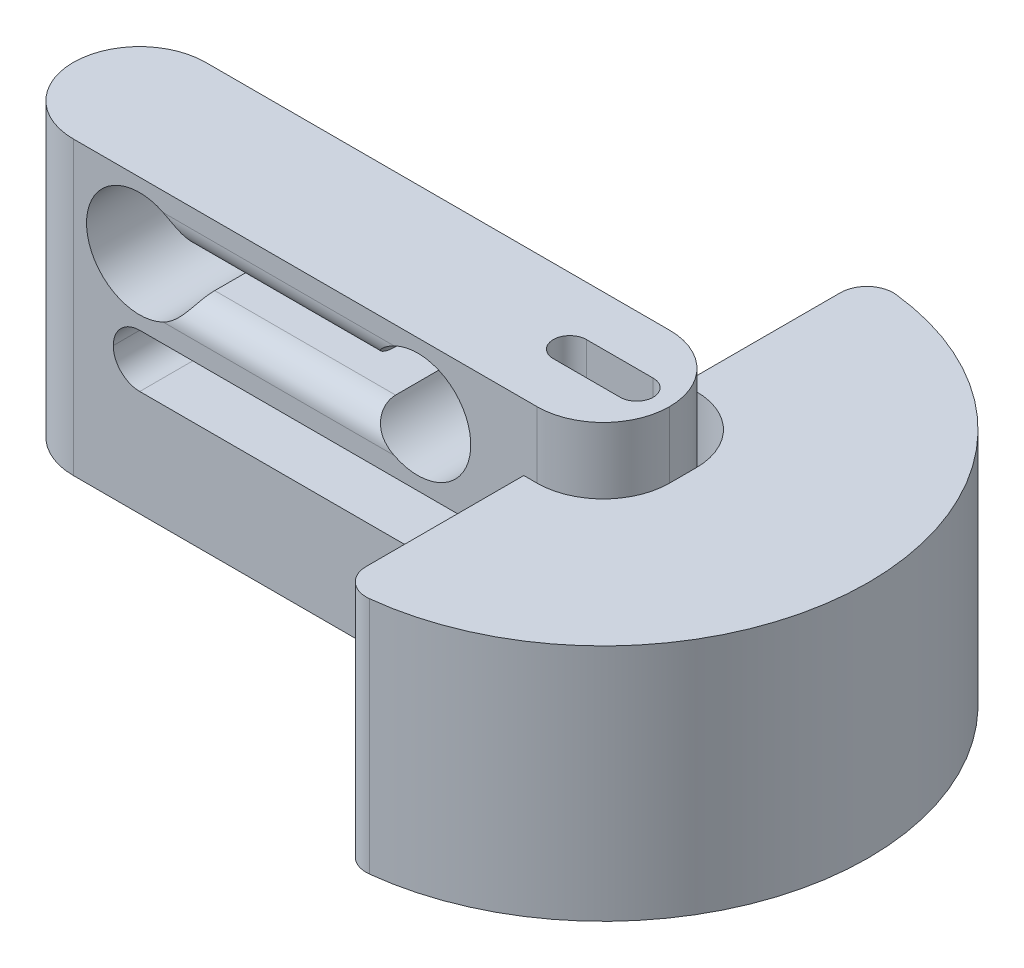
SolidWorks part; units mm, degrees
ref_plane "Front Plane" through (0, 0, 0) normal (0, 0, 1) x (1, 0, 0)
ref_plane "Top Plane" through (0, 0, 0) normal (0, 1, 0) x (1, 0, 0)
ref_plane "Right Plane" through (0, 0, 0) normal (1, 0, 0) x (0, 0, -1)
other "Center of Mass"
sketch "Sketch1" plane through (0, 0, 0) normal (0, 0, 1) x (1, 0, 0)
  line L0 (5, 0) -> (0, 0)
  line L1 (0, 0) -> (-5, 0)
  line L2 (-5, 0) -> (-35, 0)
  line L3 (5, 0) -> (5, -10)
  line L4 (5, -10) -> (-5, -10)
  line L5 (-5, -10) -> (-31.9826, -10)
  line L6 (-35, 0) -> (-40, 0)
  line L7 (-26.8791, -3.4207) -> (-11.5008, -3.4207)
  line L8 (-26.8791, -3.4207) -> (-26.8791, -6.5793)
  line L9 (-26.8791, -6.5793) -> (-11.5008, -6.5793)
  line L10 (-11.5008, -3.4207) -> (-11.5008, -6.5793)
  line L11 (-26.8791, -3.4207) -> (-11.5008, -6.5793) construction
  line L12 (-26.8791, -6.5793) -> (-11.5008, -3.4207) construction
  line L13 (-40, 0) -> (-40, -14)
  line L14 (-40, -14) -> (-31.9826, -14)
  line L15 (-31.9826, -14) -> (-31.9826, -10)
  circle A0 centre (-30, -5) radius 4
  circle A1 centre (-9, -5) radius 4
  point P12 (-19.1899, -5)
  dimension "D5" = 5
  dimension "D6" = 5
  dimension "D7" = 8
  dimension "D8" = 8
  dimension "D1" = 5
  dimension "D2" = 5
  dimension "D3" = 30
  dimension "D4" = 10
  dimension "D9" = 4
  dimension "D10" = 40
  dimension "D11" = 14
extrude "Boss-Extrude1" add sketch "Sketch1" along normal blind 5 and the other way blind 5 contours L14 L15 L5 L4 L3 L0 L1 L2 L6 L13 A1 L9 A0 L7 region at (4.5287, -5, 0)
sketch "Sketch2" plane through (0, 0, 0) normal (0, 1, 0) x (1, 0, 0)
  line L0 (-2.521, 0) -> (2.521, 0) construction
  line L1 (-2.521, 1.25) -> (2.521, 1.25)
  line L2 (-2.521, -1.25) -> (2.521, -1.25)
  arc A0 (-2.521, 1.25) -> (-2.521, -1.25) centre (-2.521, 0) ccw
  arc A1 (2.521, -1.25) -> (2.521, 1.25) centre (2.521, 0) ccw
  point P2 (0, 0)
extrude "Cut-Extrude1" cut sketch "Sketch2" against normal blind 5
sketch "Sketch3" plane through (0, 0, 0) normal (0, 1, 0) x (1, 0, 0)
  line L0 (5, -5) -> (-40, -5) construction
  line L1 (-40, 5) -> (5.8816, 5)
  line L2 (-40, 5) -> (-40, -5)
  line L3 (-40, -5) -> (5.8816, -5)
  line L4 (5.8816, 5) -> (5.8816, -5)
  line L6 (-44.7352, 22.5342) -> (0, 22.5342)
  line L7 (-44.7352, 22.5342) -> (-44.7352, -27.8282)
  line L8 (-44.7352, -27.8282) -> (0, -27.8282)
  line L9 (0, 22.5342) -> (0, -27.8282)
  circle A0 centre (0, 0) radius 20
  dimension "D1" = 40
extrude "Boss-Extrude2" add sketch "Sketch3" against normal blind 8 from offset 14 contours L9 A0 L1 L4 L3 | L1 L9 L3 L4 | L1 A0 L3 L9 | A0 L1 L2 L3 region at (-29.894, 0, 0) region at (-9.8957, 0, 0) region at (9.0612, 0, 0) region at (2.9408, 0, 0) offset against normal yes
sketch "Sketch4" plane through (0, -14, 0) normal (0, 1, 0) x (1, 0, 0)
  line L0 (5, 5) -> (-40, 5) construction
  line L1 (0, 20) -> (46.8504, 20)
  line L2 (0, 20) -> (0, -35.9681)
  line L3 (0, -35.9681) -> (46.8504, -35.9681)
  line L4 (46.8504, 20) -> (46.8504, -35.9681)
  line L5 (6, 6) -> (-6.1468, 6)
  line L6 (6, 6) -> (6, -6)
  line L7 (6, -6) -> (-6.1468, -6)
  line L8 (-6.1468, 6) -> (-6.1468, -6)
  line L9 (5, -5) -> (-40, -5) construction
  line L10 (5, 5) -> (5, -5) construction
  circle A0 centre (0, 0) radius 20
  arc M8 (0, -20) -> (0, 20) centre (0, 0) ccw
  line M9 (0, 20) -> (0, 5)
  dimension "D4" = 40
  dimension "D1" = 1
  dimension "D2" = 1
  dimension "D3" = 1
extrude "Boss-Extrude3" add sketch "Sketch4" along normal blind 10 contours L6 L7 L2 L5 M8 M9 region at (9.1986, -14, 0)
fillet "Fillet2" radius 5 6 edges at (-40, -11, -5) (-40, -11, 5) (6, -9, 6) (6, -9, -6) (5, -5, 5) (5, -5, -5)
fillet "Fillet3" radius 2 8 edges at (-19.5, -3.4207, -5) (-19.5, -6.5793, -5) (-19.5, -6.5793, 5) (-19.5, -3.4207, 5) (-31.9826, -10, 0) (-31.9826, -14, 0) (0, -13, -20) (0, -13, 20)
sketch "Sketch5" plane through (0, -22, 0) normal (0, -1, 0) x (1, 0, 0)
  line L0 (-35, 0) -> (-12, 0) construction
  line L1 (-35, 3.25) -> (-12, 3.25)
  line L2 (-35, -3.25) -> (-12, -3.25)
  line L4 (-6.5, 1.5) -> (-3.5, 1.5)
  line L5 (-6.5, 1.5) -> (-6.5, -1.5)
  line L6 (-6.5, -1.5) -> (-3.5, -1.5)
  line L7 (-3.5, 1.5) -> (-3.5, -1.5)
  line L8 (-6.5, 1.5) -> (-3.5, -1.5) construction
  line L9 (-6.5, -1.5) -> (-3.5, 1.5) construction
  line L10 (3.5, 1.5) -> (6.5, 1.5)
  line L11 (3.5, 1.5) -> (3.5, -1.5)
  line L12 (3.5, -1.5) -> (6.5, -1.5)
  line L13 (6.5, 1.5) -> (6.5, -1.5)
  line L14 (3.5, 1.5) -> (6.5, -1.5) construction
  line L15 (3.5, -1.5) -> (6.5, 1.5) construction
  arc A0 (-35, 3.25) -> (-35, -3.25) centre (-35, 0) ccw
  arc A1 (-12, -3.25) -> (-12, 3.25) centre (-12, 0) ccw
  circle A3 centre (0, 0) radius 2
  point P3 (-23.5, 0)
  point P8 (-5, 0)
  point P13 (5, 0)
  dimension "D3" = 3
  dimension "D9" = 4
  dimension "D1" = 35
  dimension "D2" = 12
  dimension "D4" = 3
  dimension "D5" = 0
  dimension "D6" = 5
  dimension "D7" = 3
  dimension "D8" = 5
extrude "Cut-Extrude2" cut sketch "Sketch5" against normal blind 4
fillet "Fillet4" radius 1 7 edges at (-23.5, -18, 3.25) (-8.75, -18, 0) (-23.5, -18, -3.25) (-38.25, -18, 0) (0, -18, -5) (0, -18, 5) (0, -22, -2)
sketch "Sketch6" plane through (0, -22, 0) normal (0, -1, 0) x (1, 0, 0)
  circle A0 centre (-35, 0) radius 3.25
extrude "Cut-Extrude3" cut sketch "Sketch6" against normal blind 5
sketch "Sketch7" plane through (0, 0, 0) normal (0, 1, 0) x (1, 0, 0)
  circle A0 centre (0, 0) radius 2
extrude "Boss-Extrude4" add sketch "Sketch7" along normal blind 3.7 from surface starting at face at (-4.548, -14, 0)
fillet "Fillet5" radius 1.6 2 edges at (0, -14, 2) (0, -10.3, 2)
